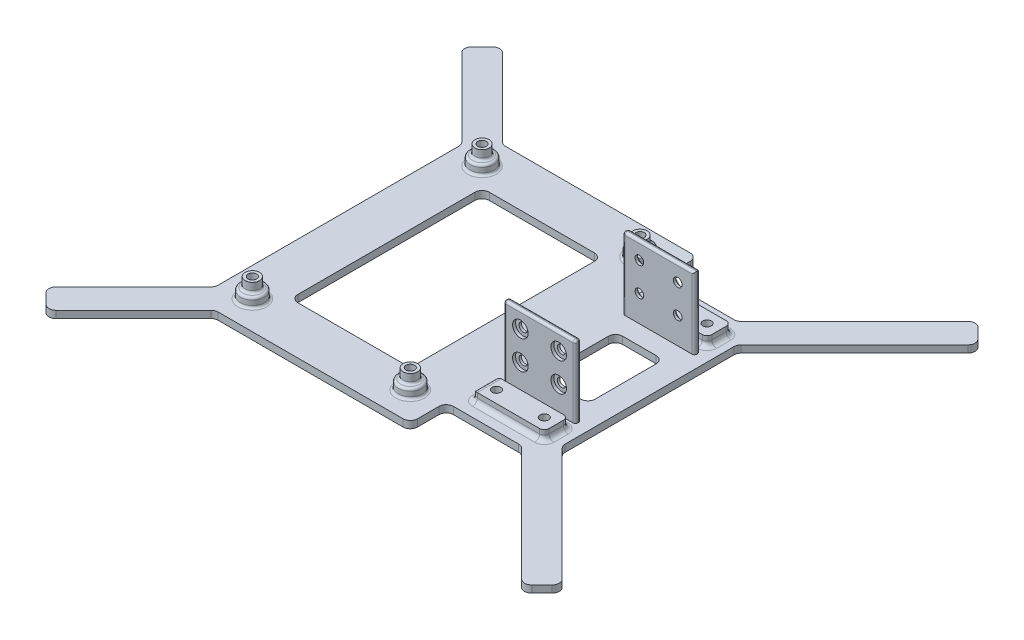
SolidWorks part; units mm, degrees
ref_plane "Front Plane" through (0, 0, 0) normal (0, 0, 1) x (1, 0, 0)
ref_plane "Top Plane" through (0, 0, 0) normal (0, 1, 0) x (1, 0, 0)
ref_plane "Right Plane" through (0, 0, 0) normal (1, 0, 0) x (0, 0, -1)
sketch "Sketch1" plane through (0, 0, 0) normal (0, 1, 0) x (1, 0, 0)
  line L0 (90, 105) -> (90, 120)
  line L1 (0, 0) -> (90, 0)
  line L2 (0, 0) -> (0, 120)
  line L3 (0, 120) -> (90, 120)
  line L4 (90, 0) -> (90, 15)
  line L5 (90, 105) -> (130, 105)
  line L7 (90, 15) -> (130, 15)
  line L8 (130, 105) -> (130, 15)
  point P9 (110, 15)
  dimension "D1" = 90
  dimension "D2" = 120
  dimension "D3" = 90
  dimension "D4" = 130
  dimension "D5" = 15
extrude "Boss-Extrude1" add sketch "Sketch1" along normal blind 3
sketch "Sketch2" plane through (0, 3, 0) normal (0, 1, 0) x (1, 0, 0)
  line L0 (0, 0) -> (90, 0) construction
  line L1 (90, 120) -> (0, 120) construction
  line L2 (0, 120) -> (0, 0) construction
  circle A0 centre (12, 108) radius 5
  circle A1 centre (78, 108) radius 5
  circle A2 centre (78, 12) radius 5
  circle A3 centre (12, 12) radius 5
  dimension "D1" = 10
  dimension "D2" = 10
  dimension "D3" = 10
  dimension "D4" = 10
  dimension "D5" = 96
  dimension "D9" = 12
  dimension "D6" = 66
  dimension "D7" = 96
  dimension "D8" = 66
  dimension "D10" = 12
  dimension "D11" = 12
extrude "Boss-Extrude2" add sketch "Sketch2" along normal blind 4
sketch "Sketch3" plane through (0, 7, 0) normal (0, 1, 0) x (1, 0, 0)
  circle A0 centre (12, 108) radius 3
  circle A1 centre (12, 12) radius 3
  circle A2 centre (78, 108) radius 3
  circle A3 centre (78, 12) radius 3
  dimension "D1" = 6
  dimension "D2" = 6
  dimension "D3" = 6
  dimension "D4" = 6
extrude "Boss-Extrude3" add sketch "Sketch3" along normal blind 4
fillet "Fillet1" radius 1 12 edges at (12, 7, -9) (12, 7, -7) (12, 3, -17) (12, 3, -113) (12, 7, -103) (12, 7, -105) (78, 3, -113) (78, 7, -103) (78, 7, -105) (78, 3, -17) (78, 7, -7) (78, 7, -9)
hole_wizard "M3 Clearance Hole1" positions "Sketch6" profile "Sketch7" hole size "M3" standard "ANSI Metric" end condition up to next
sketch "Sketch6" plane through (0, 11, 0) normal (0, 1, 0) x (1, 0, 0)
  point P0 (12, 12)
  point P4 (78, 12)
  point P7 (78, 108)
  point P10 (12, 108)
sketch "Sketch7" plane through (12, 11, -12) normal (1, 0, 0) x (0, 0, 1)
  line L0 (0, 0) -> (0, 11)
  line L1 (0, 11) -> (1.8, 11)
  line L2 (1.8, 11) -> (1.8, 0)
  line L5 (1.8, 0) -> (0, 0)
  line L11 (0, -6.35) -> (0, 107.95) construction
  dimension "Thru Hole Dia." = 3.6
  dimension "Thru Hole Depth" = 11
sketch "Sketch8" plane through (0, 0, 0) normal (0, -1, 0) x (-1, 0, 0)
  line L1 (-12, 8.4204) -> (-8.9, 10.2102)
  line L2 (-8.9, 10.2102) -> (-8.9, 13.7898)
  line L3 (-8.9, 13.7898) -> (-12, 15.5796)
  line L4 (-12, 15.5796) -> (-15.1, 13.7898)
  line L5 (-15.1, 13.7898) -> (-15.1, 10.2102)
  line L6 (-15.1, 10.2102) -> (-12, 8.4204)
  line L7 (-78, 15.5796) -> (-81.1, 13.7898)
  line L8 (-81.1, 13.7898) -> (-81.1, 10.2102)
  line L9 (-81.1, 10.2102) -> (-78, 8.4204)
  line L10 (-78, 8.4204) -> (-74.9, 10.2102)
  line L11 (-74.9, 10.2102) -> (-74.9, 13.7898)
  line L12 (-74.9, 13.7898) -> (-78, 15.5796)
  line L13 (-78, 111.5796) -> (-81.1, 109.7898)
  line L14 (-81.1, 109.7898) -> (-81.1, 106.2102)
  line L15 (-81.1, 106.2102) -> (-78, 104.4204)
  line L16 (-78, 104.4204) -> (-74.9, 106.2102)
  line L17 (-74.9, 106.2102) -> (-74.9, 109.7898)
  line L18 (-74.9, 109.7898) -> (-78, 111.5796)
  line L19 (-12, 111.5796) -> (-15.1, 109.7898)
  line L20 (-15.1, 109.7898) -> (-15.1, 106.2102)
  line L21 (-15.1, 106.2102) -> (-12, 104.4204)
  line L22 (-12, 104.4204) -> (-8.9, 106.2102)
  line L23 (-8.9, 106.2102) -> (-8.9, 109.7898)
  line L24 (-8.9, 109.7898) -> (-12, 111.5796)
  circle A0 centre (-12, 12) radius 3.1 construction
  circle A1 centre (-78, 12) radius 3.1 construction
  circle A2 centre (-78, 108) radius 3.1 construction
  circle A3 centre (-12, 108) radius 3.1 construction
  point P28 (-8.9, 108)
  dimension "D1" = 6.2
  dimension "D2" = 6.2
  dimension "D3" = 6.2
  dimension "D4" = 6.2
extrude "Cut-Extrude1" cut sketch "Sketch8" against normal blind 4
sketch "Sketch9" plane through (0, 3, 0) normal (0, 1, 0) x (1, 0, 0)
  line L0 (0, 120) -> (0, 0) construction
  line L1 (95, 86) -> (125, 86)
  line L2 (95, 86) -> (95, 83.75)
  line L3 (95, 83.75) -> (125, 83.75)
  line L4 (125, 86) -> (125, 83.75)
  line L5 (95, 36.25) -> (125, 36.25)
  line L6 (95, 36.25) -> (95, 34)
  line L7 (95, 34) -> (125, 34)
  line L8 (125, 36.25) -> (125, 34)
  line L9 (130, 105) -> (90, 105) construction
  dimension "D1" = 2.25
  dimension "D2" = 2.25
  dimension "D3" = 30
  dimension "D4" = 30
  dimension "D5" = 95
  dimension "D6" = 95
  dimension "D7" = 47.5
  dimension "D8" = 19
extrude "Boss-Extrude4" add sketch "Sketch9" along normal blind 30
fillet "Fillet4" radius 1 15 edges at (125, 33, -35.125) (110, 33, -36.25) (110, 33, -34) (95, 33, -35.125) (95, 18, -34) (95, 18, -36.25) (125, 18, -34) (125, 18, -36.25) (125, 18, -86) (125, 18, -83.75) (110, 33, -86) (110, 33, -83.75) (95, 18, -86) (95, 18, -83.75) (95, 33, -84.875)
hole_wizard "CBORE for M3 SHCS1" positions "Sketch10" profile "Sketch11" counterbore size "M3" standard "ANSI Metric" end condition up to next
sketch "Sketch10" plane through (0, 0, -34) normal (0, 0, 1) x (1, 0, 0)
  line L0 (96, 3) -> (124, 3) construction
  line L1 (95, 3) -> (95, 32) construction
  line L2 (125, 32) -> (125, 3) construction
  point P0 (102, 26)
  point P2 (118, 26)
  point P4 (118, 14)
  point P6 (102, 14)
  dimension "D1" = 11
  dimension "D2" = 12
  dimension "D3" = 12
  dimension "D4" = 7
  dimension "D5" = 16
  dimension "D6" = 7
  dimension "D7" = 7
  dimension "D8" = 16
sketch "Sketch11" plane through (102, 26, -34) normal (1, 0, 0) x (0, -1, 0)
  line L0 (0, 0) -> (0, 52)
  line L1 (0, 52) -> (1.8, 52)
  line L3 (1.8, 52) -> (1.8, 1.25)
  line L4 (1.8, 1.25) -> (3.25, 1.25)
  line L5 (3.25, 1.25) -> (3.25, 0)
  line L7 (3.25, 0) -> (0, 0)
  line L11 (0, -6.35) -> (0, 107.95) construction
  dimension "Thru Hole Dia." = 3.6
  dimension "Thru Hole Depth" = 52
  dimension "C'Bore Dia." = 6.5
  dimension "C'Bore Depth" = 1.25
ref_plane "Plane1" through (0, 0, -60) normal (0, 0, 1) x (1, 0, 0)
mirror "Mirror1" about plane through (0, 0, -60) normal (0, 0, 1) of "CBORE for M3 SHCS1"
sketch "Sketch12" plane through (0, 3, 0) normal (0, 1, 0) x (1, 0, 0)
  line L0 (0, 120) -> (0, 0) construction
  line L1 (95, 31) -> (125, 31)
  line L2 (95, 31) -> (95, 21)
  line L3 (95, 21) -> (125, 21)
  line L4 (125, 31) -> (125, 21)
  line L5 (95, 99) -> (125, 99)
  line L6 (95, 99) -> (95, 89)
  line L7 (95, 89) -> (125, 89)
  line L8 (125, 99) -> (125, 89)
  line L9 (90, 15) -> (130, 15) construction
  line L10 (130, 105) -> (90, 105) construction
  dimension "D1" = 30
  dimension "D2" = 95
  dimension "D3" = 95
  dimension "D4" = 30
  dimension "D5" = 10
  dimension "D6" = 10
  dimension "D7" = 6
  dimension "D8" = 6
extrude "Boss-Extrude5" add sketch "Sketch12" along normal blind 4
fillet "Fillet5" radius 2 17 edges at (95, 3, -94) (110, 3, -99) (110, 3, -89) (110, 3, -31) (95, 5, -31) (95, 7, -26) (95, 5, -21) (95, 3, -26) (125, 5, -99) (95, 5, -99) (95, 5, -89) (125, 5, -89) (125, 3, -94) (125, 5, -31) (125, 5, -21) (125, 3, -26) (110, 3, -21)
hole_wizard "M3 Clearance Hole2" positions "Sketch14" profile "Sketch13" hole size "M3" standard "ANSI Metric" end condition up to next
sketch "Sketch14" plane through (0, 7, 0) normal (0, 1, 0) x (1, 0, 0)
  line L0 (123, 31) -> (97, 31) construction
  line L1 (125, 23) -> (125, 29) construction
  line L2 (95, 23) -> (95, 29) construction
  line L3 (97, 21) -> (123, 21) construction
  point P0 (120, 26)
  point P6 (100, 26)
  dimension "D1" = 5
  dimension "D2" = 5
  dimension "D3" = 5
  dimension "D4" = 5
sketch "Sketch13" plane through (120, 7, -26) normal (1, 0, 0) x (0, 0, 1)
  line L0 (0, 0) -> (0, 7.001)
  line L1 (0, 7.001) -> (1.8, 7.001)
  line L2 (1.8, 7.001) -> (1.8, 0)
  line L5 (1.8, 0) -> (0, 0)
  line L11 (0, -6.35) -> (0, 107.95) construction
  dimension "Thru Hole Dia." = 3.6
  dimension "Thru Hole Depth" = 7.001
sketch "Sketch15" plane through (0, 0, 0) normal (0, -1, 0) x (1, 0, 0)
  line L1 (97.0894, -23.9163) -> (96.7402, -27.4788)
  line L2 (96.7402, -27.4788) -> (99.6507, -29.5625)
  line L3 (99.6507, -29.5625) -> (102.9106, -28.0837)
  line L4 (102.9106, -28.0837) -> (103.2598, -24.5212)
  line L5 (103.2598, -24.5212) -> (100.3493, -22.4375)
  line L6 (100.3493, -22.4375) -> (97.0894, -23.9163)
  line L7 (117.0894, -23.9163) -> (116.7402, -27.4788)
  line L8 (116.7402, -27.4788) -> (119.6507, -29.5625)
  line L9 (119.6507, -29.5625) -> (122.9106, -28.0837)
  line L10 (122.9106, -28.0837) -> (123.2598, -24.5212)
  line L11 (123.2598, -24.5212) -> (120.3493, -22.4375)
  line L12 (120.3493, -22.4375) -> (117.0894, -23.9163)
  circle A0 centre (100, -26) radius 3.1 construction
  circle A1 centre (120, -26) radius 3.1 construction
  point P10 (98.1954, -28.5206)
  dimension "D1" = 6.2
  dimension "D2" = 6.2
extrude "Cut-Extrude2" cut sketch "Sketch15" against normal blind 4
mirror "Mirror2" about plane through (0, 0, -60) normal (0, 0, 1) of "Cut-Extrude2", "M3 Clearance Hole2"
sketch "Sketch17" plane through (0, 3, 0) normal (0, 1, 0) x (1, 0, 0)
  line L0 (20, 100) -> (70, 100)
  line L1 (70, 100) -> (70, 20)
  line L2 (70, 20) -> (20, 20)
  line L3 (20, 20) -> (20, 100)
  line L4 (90, 120) -> (0, 120) construction
  line L5 (0, 120) -> (0, 0) construction
  line L7 (90, 105) -> (90, 120) construction
  line L8 (0, 0) -> (90, 0) construction
  line L9 (130, 15) -> (130, 105) construction
  line L10 (100, 75.75) -> (120, 75.75)
  line L11 (100, 75.75) -> (100, 44.25)
  line L12 (100, 44.25) -> (120, 44.25)
  line L13 (120, 75.75) -> (120, 44.25)
  line L14 (124, 36.25) -> (96, 36.25) construction
  line L15 (124, 83.75) -> (96, 83.75) construction
  point P22 (100, 60)
  dimension "D1" = 20
  dimension "D2" = 20
  dimension "D3" = 20
  dimension "D4" = 20
  dimension "D5" = 20
  dimension "D6" = 10
  dimension "D7" = 8
  dimension "D8" = 8
  dimension "D9" = 10
extrude "Cut-Extrude3" cut sketch "Sketch17" against normal through all
sketch "Sketch19" plane through (0, 3, 0) normal (0, 1, 0) x (1, 0, 0)
  line L0 (121.5147, 15) -> (171.8701, -35.3553)
  line L1 (90, 15) -> (130, 15) construction
  line L2 (0, 120) -> (0, 0) construction
  line L4 (0, 8.4853) -> (8.4853, 0)
  line L5 (0, 0) -> (90, 0) construction
  line L6 (8.4853, 0) -> (-26.8701, -35.3553)
  line L7 (-26.8701, -35.3553) -> (-35.3553, -26.8701)
  line L8 (-35.3553, -26.8701) -> (0, 8.4853)
  line L9 (171.8701, -35.3553) -> (180.3553, -26.8701)
  line L10 (180.3553, -26.8701) -> (130, 23.4853)
  line L11 (130, 15) -> (130, 105) construction
  line L12 (130, 23.4853) -> (121.5147, 15)
  dimension "D1" = 45
  dimension "D2" = 45
  dimension "D3" = 45
  dimension "D4" = 45
  dimension "D5" = 12
  dimension "D6" = 50
  dimension "D7" = 12
  dimension "D8" = 0
extrude "Boss-Extrude6" add sketch "Sketch19" against normal blind 3
ref_plane "Plane2" through (0, 0, -60) normal (0, 0, -1) x (-1, 0, 0)
mirror "Mirror3" about plane through (0, 0, -60) normal (0, 0, -1) of "Boss-Extrude6"
fillet "Fillet3" radius 3 28 edges at (90, 1.5, -15) (90, 1.5, 0) (90, 1.5, -120) (90, 1.5, -105) (20, 1.5, -20) (70, 1.5, -20) (20, 1.5, -100) (70, 1.5, -100) (120, 1.5, -75.75) (100, 1.5, -75.75) (120, 1.5, -44.25) (100, 1.5, -44.25) (121.5147, 1.5, -15) (171.8701, 1.5, 35.3553) (180.3553, 1.5, 26.8701) (130, 1.5, -23.4853) (130, 1.5, -96.5147) (180.3553, 1.5, -146.8701) (171.8701, 1.5, -155.3553) (121.5147, 1.5, -105) (8.4853, 1.5, -120) (-26.8701, 1.5, -155.3553) (-35.3553, 1.5, -146.8701) (0, 1.5, -111.5147) (0, 1.5, -8.4853) (-35.3553, 1.5, 26.8701) (-26.8701, 1.5, 35.3553) (8.4853, 1.5, 0)
